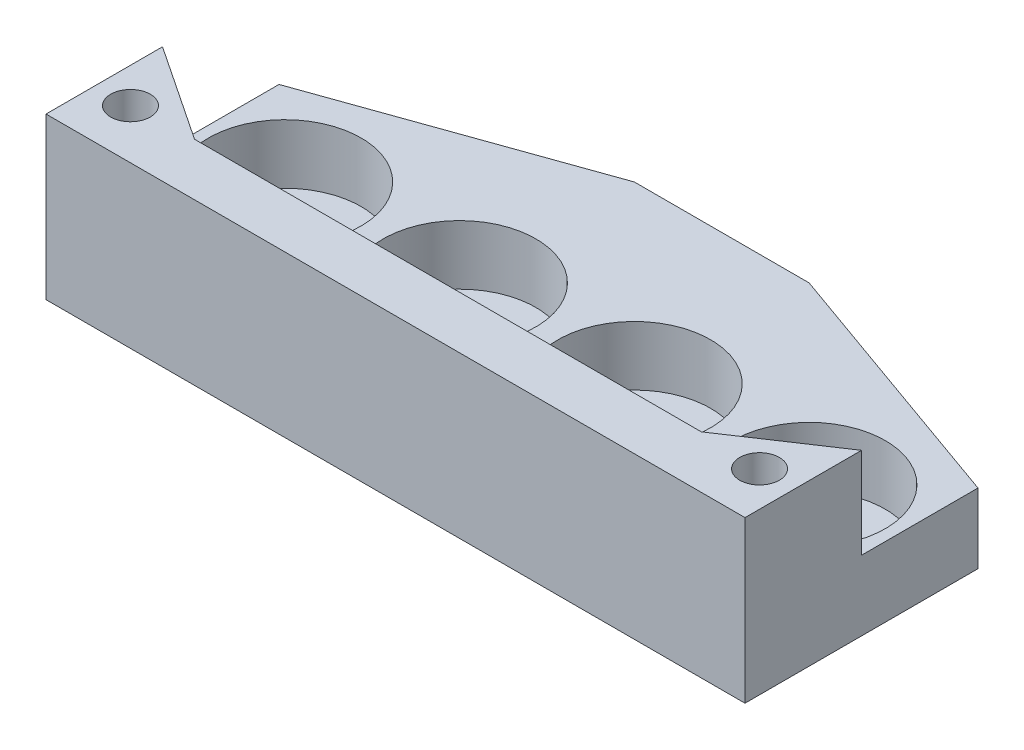
SolidWorks part; units mm, degrees
ref_plane "Front Plane" through (0, 0, 0) normal (0, 0, 1) x (1, 0, 0)
ref_plane "Top Plane" through (0, 0, 0) normal (0, 1, 0) x (1, 0, 0)
ref_plane "Right Plane" through (0, 0, 0) normal (1, 0, 0) x (0, 0, -1)
sketch "Sketch2" plane through (0, 0, 0) normal (0, 1, 0) x (1, 0, 0)
  line L0 (0, 0) -> (0, 20)
  line L1 (0, 20) -> (22.5, 28)
  line L2 (22.5, 28) -> (37.5, 28)
  line L3 (37.5, 28) -> (60, 20)
  line L4 (60, 20) -> (60, 0)
  line L5 (60, 0) -> (0, 0)
  line L6 (22.5, 13) -> (37.5, 13) construction
  line L7 (30, 28) -> (30, 0) construction
  circle A0 centre (7.5, 13) radius 2.15
  circle A1 centre (22.5, 13) radius 2.15
  circle A2 centre (37.5, 13) radius 2.15
  circle A3 centre (52.5, 13) radius 2.15
  point P17 (30, 13)
  dimension "D5" = 4.3
  dimension "D7" = 15
  dimension "D8" = 15
  dimension "D9" = 15
  dimension "D1" = 60
  dimension "D2" = 20
  dimension "D3" = 15
  dimension "D4" = 8
  dimension "D6" = 13
extrude "Boss-Extrude1" add sketch "Sketch2" along normal blind 6
sketch "Sketch3" plane through (0, 6, 0) normal (0, 1, 0) x (1, 0, 0)
  line L0 (0, 0) -> (0, 10)
  line L1 (0, 20) -> (0, 0) construction
  line L2 (0, 10) -> (15, 0)
  line L3 (0, 0) -> (60, 0) construction
  line L4 (15, 0) -> (0, 0)
  line L5 (60, 0) -> (60, 10)
  line L6 (60, 0) -> (60, 20) construction
  line L7 (60, 10) -> (45, 0)
  line L8 (45, 0) -> (60, 0)
  line L9 (51.75, 4.5) -> (8.25, 4.5)
  line M8 (0, 0) -> (60, 0)
  line M9 (60, 0) -> (60, 20)
  line M13 (0, 20) -> (0, 0)
  dimension "D1" = 15
  dimension "D2" = 10
  dimension "D3" = 4.5
extrude "Boss-Extrude2" add sketch "Sketch3" along normal blind 7.8 contours L2 M13 M8 | L7 L9 L2 M8 | L7 M9 M8 region at (5, 6, -3.3333) region at (30, 6, -2.3878) region at (55, 6, -3.3333)
sketch "Sketch4" plane through (0, 13.8, 0) normal (0, 1, 0) x (1, 0, 0)
  line L0 (0, 0) -> (60, 0) construction
  line L1 (0, 10) -> (0, 0) construction
  line L2 (60, 0) -> (60, 10) construction
  circle A0 centre (3, 4.25) radius 1.7
  circle A1 centre (57, 4.25) radius 1.7
  dimension "D1" = 3.4
  dimension "D2" = 4.25
  dimension "D3" = 3
  dimension "D4" = 3
extrude "Cut-Extrude1" cut sketch "Sketch4" against normal through all
sketch "Sketch5" plane through (0, 6, 0) normal (0, 1, 0) x (1, 0, 0)
  circle A0 centre (7.5, 13) radius 6.55
  circle A1 centre (22.5, 13) radius 6.55
  circle A2 centre (37.5, 13) radius 6.55
  circle A3 centre (52.5, 13) radius 6.55
  dimension "D1" = 13.1
extrude "Cut-Extrude2" cut sketch "Sketch5" against normal blind 5.1
